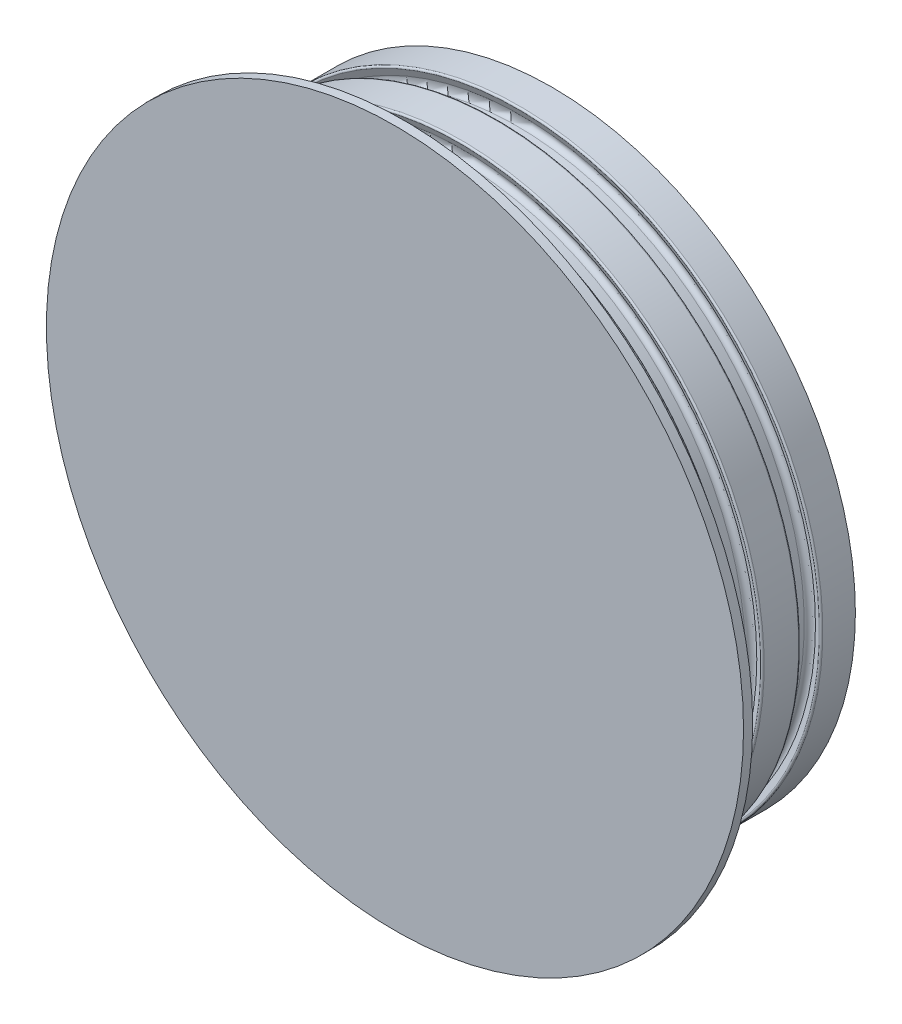
SolidWorks part; units mm, degrees
material "VeroWhite Plus"
ref_plane "Front Plane" through (0, 0, 0) normal (0, 0, 1) x (1, 0, 0)
ref_plane "Top Plane" through (0, 0, 0) normal (0, 1, 0) x (1, 0, 0)
ref_plane "Right Plane" through (0, 0, 0) normal (1, 0, 0) x (0, 0, -1)
sketch "Sketch1" plane through (0, 0, 0) normal (0, 0, 1) x (1, 0, 0)
  circle A0 centre (0, 0) radius 24.875
  dimension "D1" = 49.75
extrude "Boss-Extrude1" add sketch "Sketch1" along normal blind 12.12
sketch "Sketch2" plane through (0, 0, 0) normal (0, 1, 0) x (1, 0, 0)
  line L0 (24.875, -12.12) -> (24.875, 0) construction
  line L1 (24.875, -12.12) -> (24.875, -4.6413) construction
  line L2 (24.6963, -4.5253) -> (24.1354, -4.7751)
  line L3 (23.5771, -4.4125) -> (23.5771, -2.8969)
  line L4 (16.2677, -3.6547) -> (30.8864, -3.6547) construction
  line L5 (24.6963, -2.7841) -> (24.1354, -2.5343)
  line L6 (24.875, -4.6413) -> (24.875, -2.6681)
  line L7 (0, 0) -> (0, -23.2204) construction
  line L8 (23.9739, -2.5) -> (24.1021, -2.5) construction
  line L9 (24.875, 0) -> (-24.875, 0) construction
  line L10 (23.5771, -4.4125) -> (23.5771, -5.8363) construction
  line L11 (23.9739, -4.8094) -> (23.5771, -4.8094) construction
  line L12 (23.5771, -6.0594) -> (25.7057, -6.0594) construction
  line L13 (24.6963, -9.3346) -> (24.1354, -9.5844)
  line L14 (23.5771, -7.7062) -> (23.5771, -9.2218)
  line L15 (24.6963, -7.5934) -> (24.1354, -7.3437)
  line L16 (24.875, -7.4774) -> (24.875, -9.4507)
  line L17 (23.9739, -9.6187) -> (22.6786, -9.6187) construction
  arc A0 (24.1354, -4.7751) -> (23.5771, -4.4125) centre (23.9739, -4.4125) cw
  arc A1 (24.6963, -4.5253) -> (24.875, -4.6413) centre (24.748, -4.6413) cw
  circle A2 centre (24.4661, -3.6547) radius 0.889 construction
  arc A3 (24.1354, -2.5343) -> (23.5771, -2.8969) centre (23.9739, -2.8969) ccw
  arc A4 (24.6963, -2.7841) -> (24.875, -2.6681) centre (24.748, -2.6681) ccw
  arc A5 (24.6963, -9.3346) -> (24.875, -9.4507) centre (24.748, -9.4507) cw
  arc A6 (24.1354, -9.5844) -> (23.5771, -9.2218) centre (23.9739, -9.2218) cw
  arc A7 (24.1354, -7.3437) -> (23.5771, -7.7062) centre (23.9739, -7.7062) ccw
  arc A8 (24.6963, -7.5934) -> (24.875, -7.4774) centre (24.748, -7.4774) ccw
  point P8 (23.5771, -3.6547)
  point P15 (23.5771, -3.6547)
  point P46 (25.3551, -3.6547)
  dimension "D3" = 0.3969
  dimension "D4" = 0.127
  dimension "D5" = 1.778
  dimension "D1" = 1.2979
  dimension "D2" = 66
  dimension "D6" = 2.5
  dimension "D7" = 1.25
revolve "Cut-Revolve1" cut sketch "Sketch2" angle 360 about L7
sketch "Sketch3" plane through (0, 0, 0) normal (0, 0, -1) x (-1, 0, 0)
  circle A0 centre (0, 0) radius 23
  circle A1 centre (0, 0) radius 23.5771 construction
  circle A2 centre (0, 0) radius 23.5771 construction
  dimension "D1" = 46
extrude "Cut-Extrude1" cut sketch "Sketch3" against normal offset from surface (10.12 mm away) 2 up to face at (24.875, 0, 12.12)
sketch "Sketch4" plane through (0, 0, 10.12) normal (0, 0, -1) x (-1, 0, 0)
  line L1 (-21.9089, 7) -> (-4.9089, 7)
  line L3 (-21.9089, -7) -> (-4.9089, -7)
  line L4 (-4.9089, 7) -> (-4.9089, -7)
  line L5 (-21.9089, 7) -> (-4.9089, -7) construction
  line L6 (-21.9089, -7) -> (-4.9089, 7) construction
  circle A0 centre (0, 0) radius 23 construction
  arc A1 (-21.9089, 7) -> (-21.9089, -7) centre (0, 0) ccw
  point P0 (-13.4089, 0)
  dimension "D2" = 14
extrude "Cut-Extrude2" cut sketch "Sketch4" against normal up to surface (2 mm away) up to face at (24.875, 0, 12.12)
sketch "Sketch13" plane through (0, 0, 12.12) normal (0, 0, 1) x (1, 0, 0)
  circle A0 centre (0, 0) radius 28.575
  dimension "D1" = 57.15
extrude "Boss-Extrude11" add sketch "Sketch13" along normal blind 0.75
fillet "Fillet1" radius 3 1 edges at (4.9089, 0, 10.12)
fillet "Fillet2" radius 3 1 edges at (4.9089, 0, 12.12)
sketch "Sketch15" plane through (0, 0, 10.12) normal (0, 0, -1) x (-1, 0, 0)
  line L0 (-2.0805, 7) -> (-21.9089, 7) construction
  line L1 (-2.0805, 7) -> (-21.9089, 7) construction
  line L2 (0, 0) -> (-23, 0) construction
  line L4 (5, 14.7404) -> (15, 14.7404)
  line L5 (5, 14.7404) -> (5, -14.7404)
  line L6 (5, -14.7404) -> (15, -14.7404)
  line L7 (15, 14.7404) -> (15, -14.7404)
  line L8 (5, 14.7404) -> (15, -14.7404) construction
  line L9 (5, -14.7404) -> (15, 14.7404) construction
  circle A0 centre (-11.6425, 11) radius 2
  arc A1 (-21.9089, 7) -> (-21.9089, -7) centre (0, 0) ccw construction
  circle A2 centre (-11.6425, -11) radius 2
  point P2 (-11.6425, 9)
  point P13 (10, 0)
  dimension "D1" = 4
  dimension "D3" = 10
  dimension "D4" = 5
  dimension "D2" = 2
extrude "Cut-Extrude3" cut sketch "Sketch15" against normal blind 0.5
sketch "Sketch16" plane through (0, 0, 12.12) normal (0, 0, -1) x (-1, 0, 0)
  line L0 (-22.6225, 4.15) -> (-19.3993, 4.15)
  line L1 (-19.3993, 2.15) -> (-22.8993, 2.15)
  line L2 (-19.3993, 2.15) -> (-19.3993, -2.15) construction
  line L3 (-19.3993, -2.15) -> (-22.8993, -2.15)
  line L5 (-19.3993, 2.15) -> (-22.8993, -2.15) construction
  line L6 (-19.3993, -2.15) -> (-22.8993, 2.15) construction
  line L7 (-19.3993, 4.15) -> (-19.3993, 2.15)
  line L8 (-22.6225, -4.15) -> (-19.3993, -4.15)
  line L9 (-19.3993, -4.15) -> (-19.3993, -2.15)
  line L10 (-13.5815, 5.2635) -> (-13.5815, -5.2635) construction
  line L11 (-13.5815, 0) -> (0, 0) construction
  arc A0 (-21.9089, 7) -> (-21.9089, -7) centre (0, 0) ccw construction
  arc A1 (-22.6225, 4.15) -> (-22.8993, 2.15) centre (0, 0) ccw
  arc A2 (-22.8993, -2.15) -> (-22.6225, -4.15) centre (0, 0) ccw
  circle A3 centre (-13.5815, -2.15) radius 0.75
  circle A4 centre (-13.5815, 2.15) radius 0.75
  point P0 (-21.1493, 0)
  point P15 (-13.5815, 0)
  dimension "D5" = 1.5
  dimension "D1" = 4.3
  dimension "D2" = 3.5
  dimension "D3" = 2
  dimension "D4" = 2
extrude "Boss-Extrude12" add sketch "Sketch16" along normal up to surface (2 mm away) up to face at (-10, 0, 10.12)
sketch "Sketch17" plane through (0, 0, 10.12) normal (0, 0, -1) x (-1, 0, 0)
  line L0 (15, 14.7404) -> (5, 14.7404) construction
  line L1 (15, -14.7404) -> (15, 14.7404) construction
  line L2 (5, -14.7404) -> (15, -14.7404) construction
  line L3 (-21.9089, 7) -> (-2.0805, 7)
  line L4 (-2.0805, 7) -> (-2.0805, -7)
  line L5 (-2.0805, -7) -> (-21.9089, -7)
  line L6 (-21.9089, 7) -> (-2.0805, 7)
  line L7 (-2.0805, 7) -> (-2.0805, -7)
  line L8 (-2.0805, -7) -> (-21.9089, -7)
  line L9 (5, 14.7404) -> (5, -14.7404) construction
  line L10 (15, 14.7404) -> (5, 14.7404)
  line L11 (15, -14.7404) -> (15, 14.7404)
  line L12 (5, -14.7404) -> (15, -14.7404)
  line L13 (5, 14.7404) -> (5, -14.7404)
  circle A0 centre (-11.6425, 11) radius 2 construction
  arc A1 (-21.9089, -7) -> (-21.9089, 7) centre (0, 0) ccw
  arc A2 (-21.9089, -7) -> (-21.9089, 7) centre (0, 0) ccw
  circle A3 centre (-11.6425, -11) radius 2 construction
  circle A4 centre (-11.6425, 11) radius 2
  circle A5 centre (-11.6425, -11) radius 2
  dimension "D1" = 0
